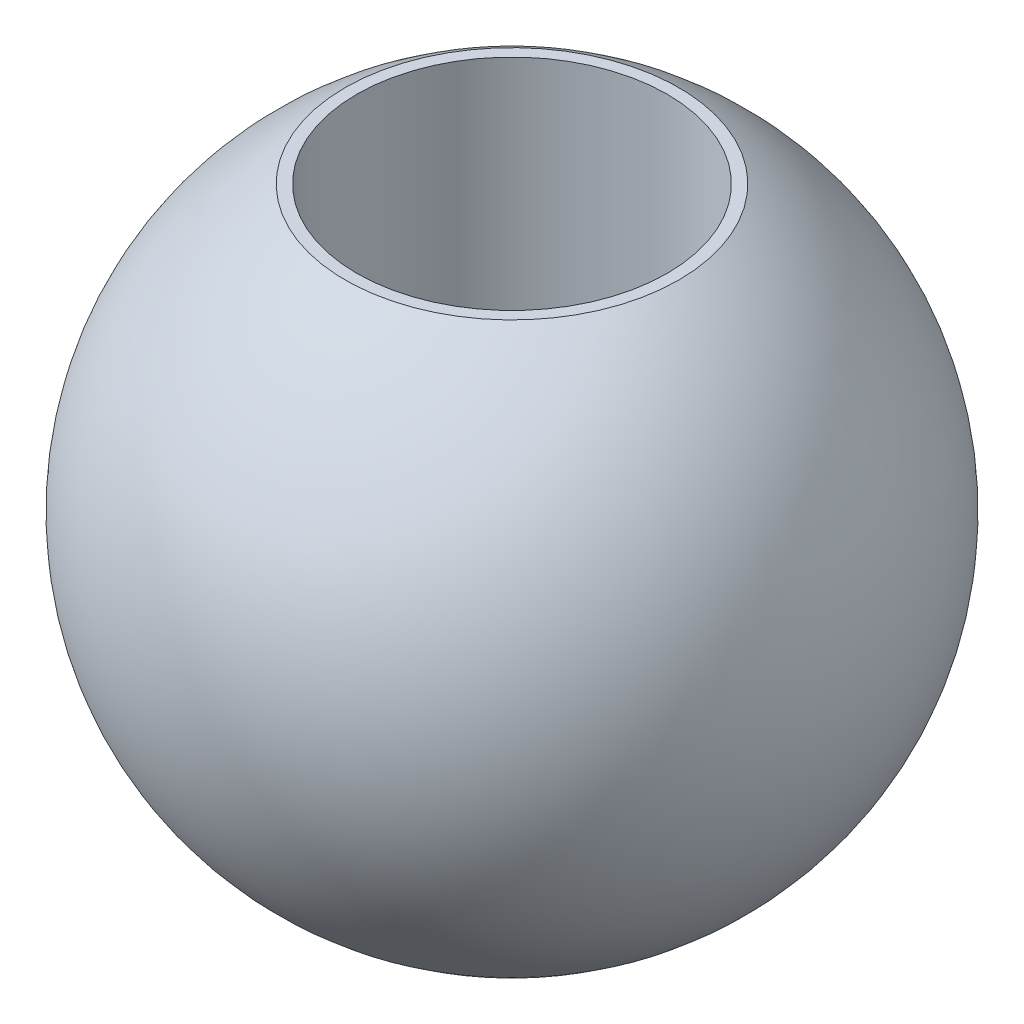
SolidWorks part; units mm, degrees
ref_plane "Front Plane" through (0, 0, 0) normal (0, 0, 1) x (1, 0, 0)
ref_plane "Top Plane" through (0, 0, 0) normal (0, 1, 0) x (1, 0, 0)
ref_plane "Right Plane" through (0, 0, 0) normal (1, 0, 0) x (0, 0, -1)
sketch "Sketch1" plane through (0, 0, 0) normal (0, 0, 1) x (1, 0, 0)
  line L0 (-3.2455, 5.9703) -> (3.2455, -5.9703)
  arc A0 (3.2455, -5.9703) -> (-3.2455, 5.9703) centre (0, 0) ccw
revolve "Revolve1" add sketch "Sketch1" angle 360 about L0
sketch "Sketch4" plane through (0, 0, 0) normal (0, 0, 1) x (1, 0, 0)
  line L0 (0, 8.5552) -> (0, -8.3966) construction
  line L1 (8.16, 8.5716) -> (-8.7167, 8.5552)
  line L4 (8.16, 8.5716) -> (8.16, 5.8614)
  line L5 (8.16, 5.8614) -> (-8.7167, 5.8614)
  line L6 (-8.7167, 8.5552) -> (-8.7167, 5.8614)
  line L7 (0, -1.0708) -> (7.7204, -1.0708) construction
  line L8 (0, -8.3966) -> (-8.7167, -8.135)
  line L9 (0, -8.3966) -> (8.16, -8.3966)
  line L10 (8.16, -8.3966) -> (8.16, -5.86)
  line L11 (8.16, -5.86) -> (-8.7167, -5.86)
  line L12 (-8.7167, -5.86) -> (-8.7167, -8.135)
extrude "Cut-Extrude3" cut sketch "Sketch4" against normal blind 10 and the other way blind 10
sketch "Sketch6" plane through (0, 5.8614, 0) normal (0, 1, 0) x (1, 0, 0)
  circle A0 centre (0, 0) radius 3.2
extrude "Cut-Extrude5" cut sketch "Sketch6" against normal up to surface (11.7214 mm away) up to face at (0, -5.86, -3.4407)
sketch "Sketch7" plane through (0, 0, 0) normal (0, 0, 1) x (1, 0, 0)
  line L0 (0.05, 0) -> (0.0778, 0)
  line L1 (-0.05, 0) -> (-0.0778, 0)
  line L2 (0, 0) -> (0.0284, 0) construction
  arc A0 (0.0778, 0) -> (-0.0778, 0) centre (0, 0) cw
  arc A1 (0.05, 0) -> (-0.05, 0) centre (0, 0) cw
revolve "Revolve2" add sketch "Sketch7" angle 360 about L2
